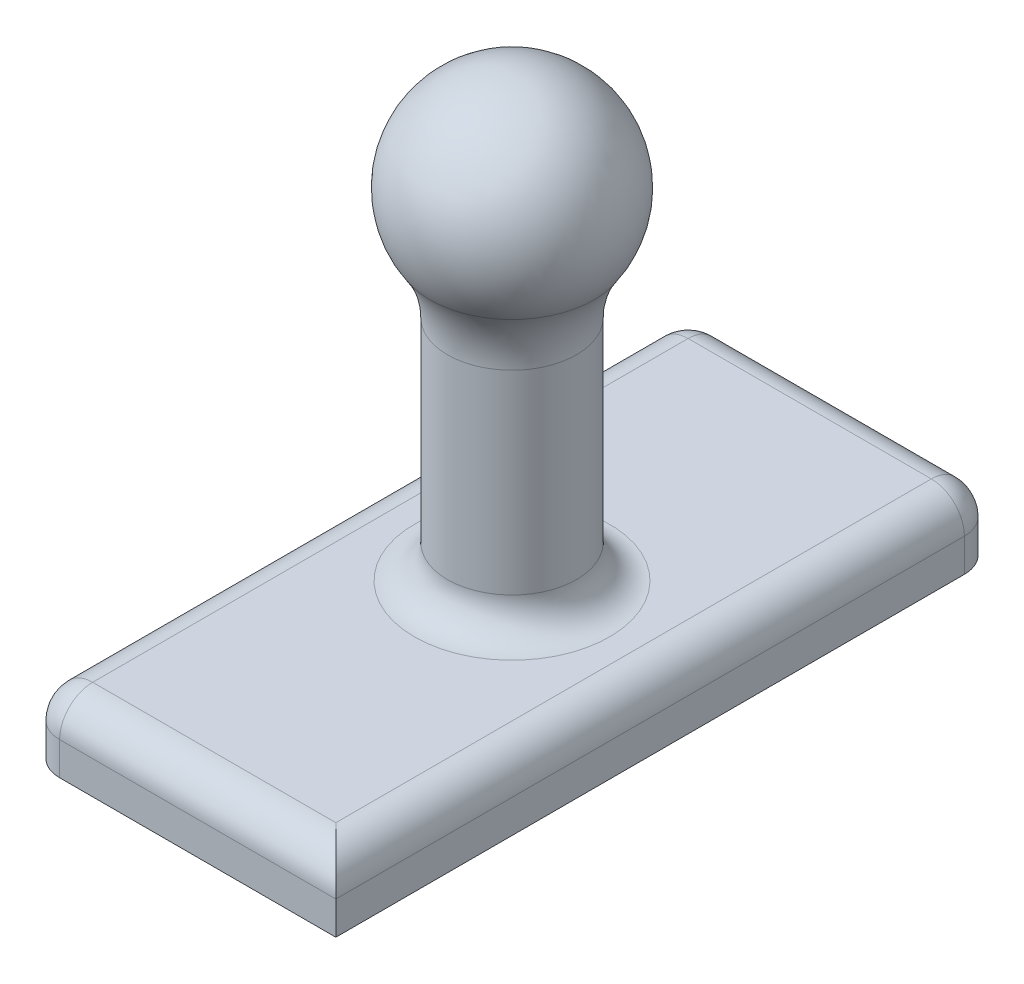
SolidWorks part; units mm, degrees
ref_plane "Alzado" through (0, 0, 0) normal (0, 0, 1) x (1, 0, 0)
ref_plane "Planta" through (0, 0, 0) normal (0, 1, 0) x (1, 0, 0)
ref_plane "Vista lateral" through (0, 0, 0) normal (1, 0, 0) x (0, 0, -1)
sketch "Croquis2" plane through (0, 0, 0) normal (0, 1, 0) x (1, 0, 0)
  circle A0 centre (0, 0) radius 1.95
  dimension "D1" = 3.9
extrude "Saliente-Extruir1" add sketch "Croquis2" along normal blind 8 contours A0
dome "Cúpula1" faces to dome 1 distance 5.3 reverse direction no elliptical dome no face at (0, 8, 1.95) parameters "D1"=5.3
sketch "Croquis11" plane through (0, 0, 0) normal (0, -1, 0) x (-1, 0, 0)
  line L1 (4.675, 10) -> (-4.675, 10)
  line L2 (4.675, 10) -> (4.675, -10)
  line L3 (4.675, -10) -> (-4.675, -10)
  line L4 (-4.675, 10) -> (-4.675, -10)
  line L5 (4.675, 10) -> (-4.675, -10) construction
  line L6 (4.675, -10) -> (-4.675, 10) construction
  point P0 (0, 0)
  dimension "D1" = 20
  dimension "D2" = 9.35
extrude "Saliente-Extruir3" add sketch "Croquis11" along normal blind 2 contours L1 L4 L3 L2
fillet "Fillet1" radius 1 5 edges at (0, 0, -10) (4.675, 0, 0) (0, 0, 10) (-4.675, 0, 0) (0, 0, 1.95)
fillet "Fillet2" radius 1 6 edges at (-4.3821, -0.2929, 9.7071) (4.3821, -0.2929, -9.7071) (-4.3821, -0.2929, -9.7071) (-4.675, -1.5, 10) (4.675, -1.5, -10) (-4.675, -1.5, -10)
fillet "Fillet3" radius 3 1 edges at (0, 8, 1.95)
